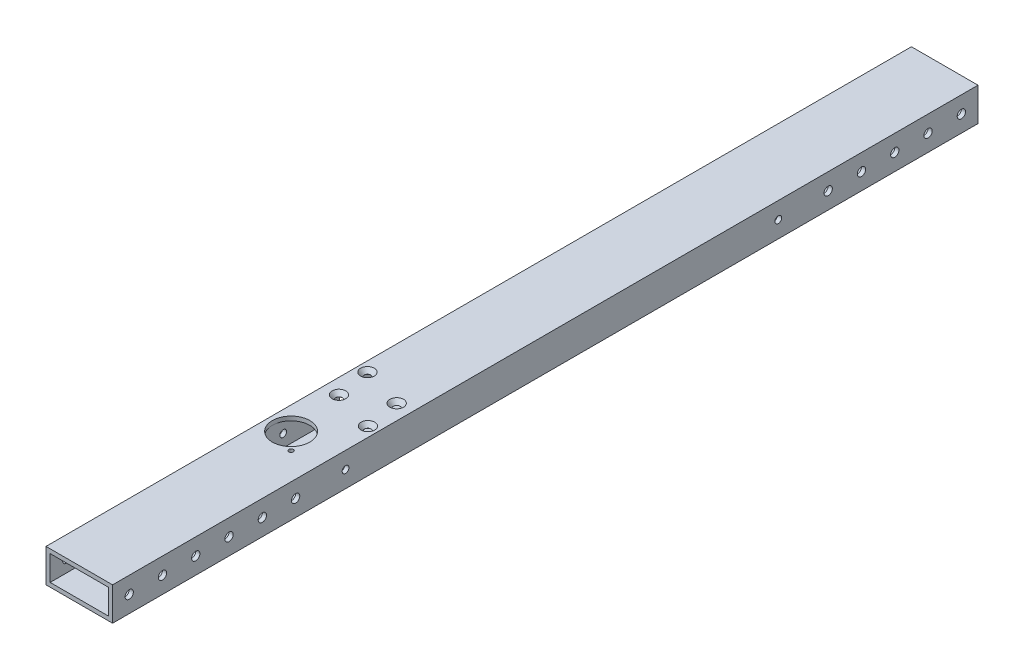
SolidWorks part; units mm, degrees
material "6061 Alloy"
ref_plane "Front Plane" through (0, 0, 0) normal (0, 0, 1) x (1, 0, 0)
ref_plane "Top Plane" through (0, 0, 0) normal (0, 1, 0) x (1, 0, 0)
ref_plane "Right Plane" through (0, 0, 0) normal (1, 0, 0) x (0, 0, -1)
sketch "Sketch1" plane through (0, 0, 0) normal (0, 0, 1) x (1, 0, 0)
  line L0 (-22.225, 9.525) -> (22.225, 9.525)
  line L2 (-25.4, 12.7) -> (25.4, 12.7)
  line L3 (-25.4, 12.7) -> (-25.4, -12.7)
  line L4 (-25.4, -12.7) -> (25.4, -12.7)
  line L5 (25.4, 12.7) -> (25.4, -12.7)
  line L10 (22.225, 9.525) -> (22.225, -9.525)
  line L11 (-22.225, -9.525) -> (22.225, -9.525)
  line L12 (-22.225, 9.525) -> (-22.225, -9.525)
  point P12 (0, 12.7)
  point P14 (25.4, 0)
  dimension "Wall Thickness" = 3.175
  dimension "Outside Width" = 50.8
  dimension "Outside Height" = 25.4
  dimension "Inside Height" = 19.05
  dimension "Inside Width" = 44.45
sketch "Sketch2" plane through (0, 0, 0) normal (1, 0, 0) x (0, 0, -1)
  line L0 (330.2, 0) -> (-330.2, 0)
  point P4 (0, 0)
  point P7 (-330.2, 0)
  point P10 (330.2, 0)
  dimension "Length" = 660.4
sketch "Sketch3" plane through (0, 0, 0) normal (0, 0, 1) x (1, 0, 0)
  line L21 (25.4, 12.7) -> (-25.4, 12.7)
  line L22 (25.4, -12.7) -> (25.4, 12.7)
  line L23 (-25.4, -12.7) -> (25.4, -12.7)
  line L24 (-25.4, 12.7) -> (-25.4, -12.7)
  line L25 (25.4, 12.7) -> (-25.4, 12.7)
  line L26 (25.4, -12.7) -> (25.4, 12.7)
  line L27 (-25.4, -12.7) -> (25.4, -12.7)
  line L28 (-25.4, 12.7) -> (-25.4, -12.7)
  line L29 (22.225, 9.525) -> (-22.225, 9.525)
  line L30 (22.225, -9.525) -> (22.225, 9.525)
  line L31 (-22.225, -9.525) -> (22.225, -9.525)
  line L32 (-22.225, 9.525) -> (-22.225, -9.525)
  line L33 (22.225, 9.525) -> (-22.225, 9.525)
  line L34 (22.225, -9.525) -> (22.225, 9.525)
  line L35 (-22.225, -9.525) -> (22.225, -9.525)
  line L36 (-22.225, 9.525) -> (-22.225, -9.525)
  dimension "D1" = 0
  dimension "D2" = 0
extrude "Boss-Extrude1" add sketch "Sketch3" along normal up to vertex (330.2 mm away) and the other way up to vertex (330.2 mm away) up to point (0, 0, 330.2) other way up to point (0, 0, -330.2)
sketch "Drawing Reference" plane through (0, 0, 0) normal (1, 0, 0) x (0, 0, -1)
  line L0 (-330.2, 0) -> (330.2, 0) construction
  line L1 (0, -12.7) -> (0, 12.7) construction
  line L2 (-330.2, -12.7) -> (330.2, -12.7) construction
  line L5 (-330.2, 12.7) -> (330.2, 12.7) construction
  point P7 (-293.624, 0)
  point P8 (293.624, 0)
  dimension "D1" = 36.576
sketch "Sketch5" plane through (25.4, 0, 0) normal (1, 0, 0) x (0, 0, -1)
  line L2 (-266.7, 0) -> (-241.3, 0)
  line L3 (-241.3, 0) -> (-215.9, 0)
  line L4 (-215.9, 0) -> (-190.5, 0)
  line L5 (-317.5, 0) -> (-330.2, 0)
  line L6 (-330.2, -12.7) -> (-330.2, 12.7) construction
  line L7 (-317.5, 0) -> (-292.1, 0)
  line L8 (-292.1, 0) -> (-266.7, 0)
sketch "Sketch8" plane through (25.4, 0, 0) normal (1, 0, 0) x (0, 0, -1)
  line L0 (330.2, 0) -> (292.1, 0)
  line L1 (330.2, -12.7) -> (330.2, 12.7) construction
  line L2 (292.1, 0) -> (266.7, 0)
  line L3 (266.7, 0) -> (241.3, 0)
  line L4 (241.3, 0) -> (215.9, 0)
  line L5 (330.2, 0) -> (317.5, 0)
hole_wizard "1/4 (0.25) Diameter Hole3" positions "Sketch12" profile "Sketch13" hole size "1/4" standard "ANSI Inch" end condition through all
sketch "Sketch12" plane through (-25.4, 0, 0) normal (-1, 0, 0) x (0, 0, 1)
  point P4 (-317.5, 0)
sketch "Sketch13" plane through (-25.4, 0, -317.5) normal (0, 1, 0) x (0, 0, 1)
  line L0 (0, 0) -> (0, 50.8)
  line L1 (0, 50.8) -> (3.175, 50.8)
  line L2 (3.175, 50.8) -> (3.175, 0)
  line L5 (3.175, 0) -> (0, 0)
  line L11 (0, -6.35) -> (0, 107.95) construction
  dimension "Thru Hole Dia." = 6.35
  dimension "Thru Hole Depth" = 50.8
hole_wizard "1/4 (0.25) Diameter Hole4" positions "Sketch14" profile "Sketch15" hole size "1/4" standard "ANSI Inch" end condition through all
sketch "Sketch14" plane through (-25.4, 0, 0) normal (-1, 0, 0) x (0, 0, 1)
  point P0 (292.1, 0)
  point P3 (317.5, 0)
sketch "Sketch15" plane through (-25.4, 0, 292.1) normal (0, 1, 0) x (0, 0, 1)
  line L0 (0, 0) -> (0, 50.8)
  line L1 (0, 50.8) -> (3.175, 50.8)
  line L2 (3.175, 50.8) -> (3.175, 0)
  line L5 (3.175, 0) -> (0, 0)
  line L11 (0, -6.35) -> (0, 107.95) construction
  dimension "Thru Hole Dia." = 6.35
  dimension "Thru Hole Depth" = 50.8
hole_wizard "1/4 (0.25) Diameter Hole5" positions "Sketch17" profile "Sketch18" hole size "1/4" standard "ANSI Inch" end condition through all
sketch "Sketch17" plane through (25.4, 0, 0) normal (1, 0, 0) x (0, 0, -1)
  point P0 (292.1, 0)
  point P3 (266.7, 0)
sketch "Sketch18" plane through (25.4, 0, -292.1) normal (0, 1, 0) x (0, 0, -1)
  line L0 (0, 0) -> (0, 50.8)
  line L1 (0, 50.8) -> (3.175, 50.8)
  line L2 (3.175, 50.8) -> (3.175, 0)
  line L5 (3.175, 0) -> (0, 0)
  line L11 (0, -6.35) -> (0, 107.95) construction
  dimension "Thru Hole Dia." = 6.35
  dimension "Thru Hole Depth" = 50.8
hole_wizard "1/4 (0.25) Diameter Hole6" positions "Sketch19" profile "Sketch20" hole size "1/4" standard "ANSI Inch" end condition through all
sketch "Sketch19" plane through (25.4, 0, 0) normal (1, 0, 0) x (0, 0, -1)
  point P0 (215.9, 0)
  point P3 (241.3, 0)
sketch "Sketch20" plane through (25.4, 0, -215.9) normal (0, 1, 0) x (0, 0, -1)
  line L0 (0, 0) -> (0, 50.8)
  line L1 (0, 50.8) -> (3.175, 50.8)
  line L2 (3.175, 50.8) -> (3.175, 0)
  line L5 (3.175, 0) -> (0, 0)
  line L11 (0, -6.35) -> (0, 107.95) construction
  dimension "Thru Hole Dia." = 6.35
  dimension "Thru Hole Depth" = 50.8
hole_wizard "1/4 (0.25) Diameter Hole7" positions "Sketch21" profile "Sketch22" hole size "1/4" standard "ANSI Inch" end condition through all
sketch "Sketch21" plane through (25.4, 0, 0) normal (1, 0, 0) x (0, 0, -1)
  point P0 (-190.5, 0)
  point P3 (-215.9, 0)
sketch "Sketch22" plane through (25.4, 0, 190.5) normal (0, 1, 0) x (0, 0, -1)
  line L0 (0, 0) -> (0, 50.8)
  line L1 (0, 50.8) -> (3.175, 50.8)
  line L2 (3.175, 50.8) -> (3.175, 0)
  line L5 (3.175, 0) -> (0, 0)
  line L11 (0, -6.35) -> (0, 107.95) construction
  dimension "Thru Hole Dia." = 6.35
  dimension "Thru Hole Depth" = 50.8
hole_wizard "1/4 (0.25) Diameter Hole8" positions "Sketch23" profile "Sketch24" hole size "1/4" standard "ANSI Inch" end condition through all
sketch "Sketch23" plane through (25.4, 0, 0) normal (1, 0, 0) x (0, 0, -1)
  point P0 (-266.7, 0)
  point P3 (-241.3, 0)
sketch "Sketch24" plane through (25.4, 0, 266.7) normal (0, 1, 0) x (0, 0, -1)
  line L0 (0, 0) -> (0, 50.8)
  line L1 (0, 50.8) -> (3.175, 50.8)
  line L2 (3.175, 50.8) -> (3.175, 0)
  line L5 (3.175, 0) -> (0, 0)
  line L11 (0, -6.35) -> (0, 107.95) construction
  dimension "Thru Hole Dia." = 6.35
  dimension "Thru Hole Depth" = 50.8
sketch "Sketch25" plane through (25.4, 0, 0) normal (1, 0, 0) x (0, 0, -1)
  line L0 (-190.5, 0) -> (-152.4, 0)
  line L1 (215.9, 0) -> (177.8, 0)
hole_wizard "13/64 (0.20313) Diameter Hole1" positions "Sketch26" profile "Sketch27" hole size "13/64" standard "ANSI Inch" end condition through all
sketch "Sketch26" plane through (25.4, 0, 0) normal (1, 0, 0) x (0, 0, -1)
  point P0 (-152.4, 0)
  point P3 (177.8, 0)
sketch "Sketch27" plane through (25.4, 0, 152.4) normal (0, 1, 0) x (0, 0, -1)
  line L0 (0, 0) -> (0, 50.8)
  line L1 (0, 50.8) -> (2.5798, 50.8)
  line L2 (2.5798, 50.8) -> (2.5798, 0)
  line L5 (2.5798, 0) -> (0, 0)
  line L11 (0, -6.35) -> (0, 107.95) construction
  dimension "Thru Hole Dia." = 5.1595
  dimension "Thru Hole Depth" = 50.8
sketch "Sketch30" plane through (-25.4, 0, 0) normal (-1, 0, 0) x (0, 0, 1)
  point P0 (-128.5875, 0)
  point P1 (-103.1875, 0)
  point P2 (77.7875, 0)
  point P3 (103.1875, 0)
hole_wizard "1/2 (0.5) Diameter Hole1" positions "Sketch33" profile "Sketch34" hole size "1/2" standard "ANSI Inch"
sketch "Sketch33" plane through (-25.4, 0, 0) normal (-1, 0, 0) x (0, 0, 1)
  point P0 (-128.5875, 0)
  point P3 (-103.1875, 0)
  point P7 (77.7875, 0)
  point P10 (103.1875, 0)
sketch "Sketch34" plane through (-25.4, 0, -128.5875) normal (0, 1, 0) x (0, 0, 1)
  line L0 (0, 0) -> (0, 10.1655)
  line L1 (0, 10.1655) -> (6.35, 6.35)
  line L2 (6.35, 6.35) -> (6.35, 0)
  line L5 (6.35, 0) -> (0, 0)
  line L10 (0, 10.1655) -> (-6.35, 6.35) construction
  line L11 (0, -6.35) -> (0, 107.95) construction
  dimension "Hole Dia." = 12.7
  dimension "Hole Depth" = 6.35
  dimension "Drill Angle" = 118
sketch "Sketch37" plane through (0, -12.7, 0) normal (0, -1, 0) x (1, 0, 0)
  line L1 (13.819, 101.7821) -> (17.931, 127.883) construction
  line L5 (-13.819, 118.2319) -> (17.931, 127.883) construction
  line L6 (-17.931, 92.3773) -> (13.819, 101.7821) construction
  line L7 (-13.819, 118.2319) -> (-17.931, 92.3773) construction
hole_wizard "#10 Clearance Hole4" positions "Sketch45" profile "Sketch46" hole size "#10" standard "ANSI Inch" end condition through all
sketch "Sketch45" plane through (0, -12.7, 0) normal (0, -1, 0) x (-1, 0, 0)
  point P0 (-13.819, -101.7821)
  point P3 (-17.931, -127.883)
  point P6 (13.819, -118.2319)
  point P9 (17.931, -92.3773)
sketch "Sketch46" plane through (13.819, -12.7, 101.7821) normal (1, 0, 0) x (0, 0, -1)
  line L0 (0, 0) -> (0, 25.4)
  line L1 (0, 25.4) -> (5.2197, 25.4)
  line L2 (2.4892, 22.2589) -> (2.4892, 0)
  line L5 (2.4892, 0) -> (0, 0)
  line L7 (5.2197, 25.4) -> (2.4892, 22.2589)
  line L8 (-5.2197, 25.4) -> (-2.4892, 22.2589) construction
  line L11 (0, -6.35) -> (0, 107.95) construction
  dimension "Thru Hole Dia." = 4.9784
  dimension "Thru Hole Depth" = 25.4
  dimension "Far C'Sink Dia." = 10.4394
  dimension "Far C'Sink Angle" = 82
sketch "Sketch47" plane through (0, -12.7, 0) normal (0, -1, 0) x (1, 0, 0)
  line L0 (25.4, 144.0217) -> (-25.4, 128.9741) construction
  line L1 (25.4, 330.2) -> (25.4, -330.2) construction
  line L2 (-25.4, 128.9741) -> (575.1111, 306.8536) construction
  line L3 (-25.4, 128.9741) -> (-25.4, 180.922) construction
  line L4 (-25.4, 330.2) -> (-25.4, -330.2) construction
  line L5 (-22.225, 128.9741) -> (-22.225, 180.922) construction
  line L6 (22.2439, 154.6766) -> (-28.5561, 139.629) construction
  line L7 (-7.9375, 160.6376) -> (4.8145, 173.3896) construction
  circle A0 centre (-7.9375, 160.6376) radius 14.2875
  dimension "D1" = 3.175
  dimension "D2" = 11.1125
extrude "Cut-Extrude1" cut sketch "Sketch47" against normal through all
hole_wizard "Tap Drill for #8-32 Tap1" positions "Sketch48" profile "Sketch49" hole size "#8-32" standard "ANSI Inch" end condition through all
sketch "Sketch48" plane through (0, -12.7, 0) normal (0, -1, 0) x (-1, 0, 0)
  point P0 (-4.8145, -173.3896)
sketch "Sketch49" plane through (4.8145, -12.7, 173.3896) normal (1, 0, 0) x (0, 0, -1)
  line L0 (0, 0) -> (0, 25.4)
  line L1 (0, 25.4) -> (1.7272, 25.4)
  line L2 (1.7272, 25.4) -> (1.7272, 0)
  line L5 (1.7272, 0) -> (0, 0)
  line L11 (0, -6.35) -> (0, 107.95) construction
  dimension "Thru Hole Dia." = 3.4544
  dimension "Thru Hole Depth" = 25.4
equation "\"D1@Drawing Reference\"=\"Outside Width@Sketch1\" * 0.72"
